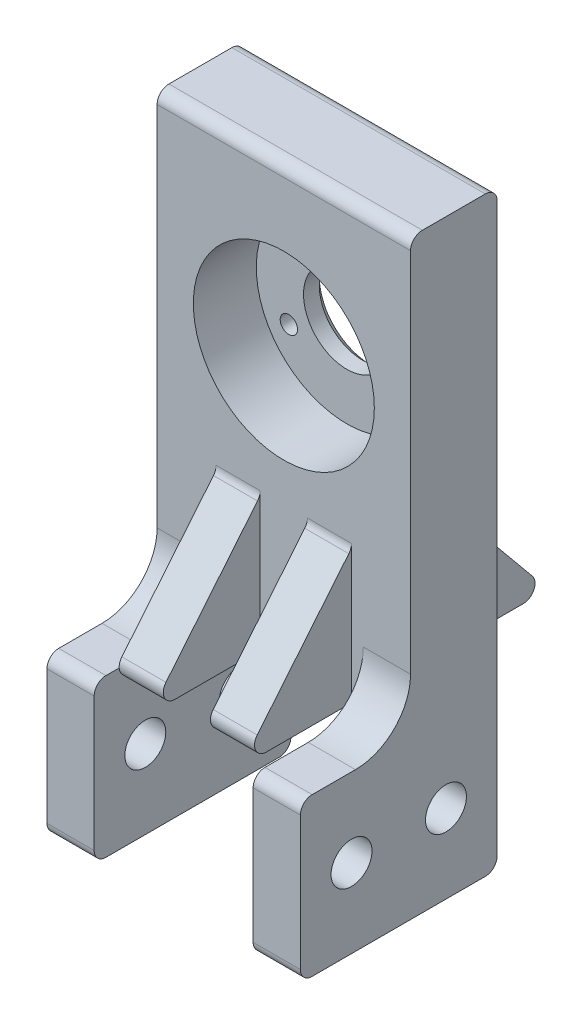
SolidWorks part; units mm, degrees
ref_plane "Front plane" through (0, 0, 0) normal (0, 0, 1) x (1, 0, 0)
ref_plane "Top plane" through (0, 0, 0) normal (0, 1, 0) x (1, 0, 0)
ref_plane "Right plane" through (0, 0, 0) normal (1, 0, 0) x (0, 0, -1)
ref_axis "Axis X" through (0, 0, 0) along (1, 0, 0)
ref_axis "Axis Y" through (0, 0, 0) along (0, 1, 0)
ref_axis "Axis Z" through (0, 0, 0) along (0, 0, 1)
sketch "Sketch1" plane through (0, 0, 0) normal (1, 0, 0) x (0, 0, -1)
  line L1 (5.5, 65.1) -> (-5.5, 65.1)
  line L2 (5.5, 65.1) -> (5.5, 10.1)
  line L3 (5.5, 10.1) -> (-5.5, 10.1)
  line L4 (-5.5, 65.1) -> (-5.5, 10.1)
  line L5 (5.5, 65.1) -> (-5.5, 10.1) construction
  line L6 (5.5, 10.1) -> (-5.5, 65.1) construction
  point P0 (0, 37.6)
  dimension "D1" = 10.1
  dimension "D2" = 11
  dimension "D3" = 55
extrude "Extrude1" add sketch "Sketch1" along normal blind 10.1 and the other way blind 10.1
sketch "Sketch2" plane through (10.1, 0, 0) normal (1, 0, 0) x (0, 0, -1)
  line L0 (5.5, 10.1) -> (5.5, 65.1) construction
  line L1 (19.5, 10) -> (12.5, 10) construction
  line L2 (19.5, 10) -> (19.5, -10) construction
  line L3 (19.5, -10) -> (-19.5, -10) construction
  line L4 (-19.5, 10) -> (-19.5, -10)
  line L5 (19.5, 10) -> (-19.5, -10) construction
  line L6 (19.5, -10) -> (-19.5, 10) construction
  line L7 (-5.5, 65.1) -> (5.5, 65.1)
  line L8 (-5.5, 65.1) -> (-5.5, 17)
  line L9 (-5.5, 10) -> (5.5, 10) construction
  line L10 (5.5, 65.1) -> (5.5, 17)
  line L11 (-12.5, 10) -> (-19.5, 10)
  line L12 (5.5, 10) -> (-5.5, 10) construction
  line L13 (5.5, 17) -> (5.5, -10)
  line L14 (-19.5, -10) -> (5.5, -10)
  arc A0 (12.5, 10) -> (5.5, 17) centre (12.5, 17) cw construction
  arc A1 (-12.5, 10) -> (-5.5, 17) centre (-12.5, 17) ccw
  point P0 (0, 0)
  dimension "D3" = 7
  dimension "D1" = 20
  dimension "D2" = 25
extrude "Extrude2" add sketch "Sketch2" along normal blind 6
mirror "Mirror2" about plane through (0, 0, 0) normal (1, 0, 0) of "Extrude2"
sketch "Sketch5" plane through (0, 0, 5.5) normal (0, 0, 1) x (1, 0, 0)
  line L0 (-16.1, 19.5) -> (16.1, 19.5) construction
  line L1 (-16.1, 65.1) -> (-16.1, 17) construction
  line L2 (16.1, 65.1) -> (16.1, 17) construction
  line L3 (-16.1, 22.3) -> (16.1, 22.3) construction
  line L4 (-16.1, 16.7) -> (16.1, 16.7) construction
  line L5 (-16.1, 54.55) -> (16.1, 54.55) construction
  line L6 (-16.1, 51.75) -> (16.1, 51.75) construction
  line L7 (-16.1, 48.95) -> (16.1, 48.95) construction
  line L8 (-5.5, 44) -> (5.5, 44) construction
  line L9 (-10.1, 10) -> (10.1, 10) construction
  line L10 (-10.1, 10) -> (-10.1, -10) construction
  line L11 (10.1, 10) -> (10.1, -10) construction
  circle A0 centre (0, 44) radius 5.5
  dimension "D5" = 11
  dimension "D1" = 5.6
  dimension "D2" = 5.6
  dimension "D3" = 19.5
  dimension "D4" = 32.25
  dimension "D7" = 10
  dimension "D8" = 34
extrude "Extrude4" cut sketch "Sketch5" against normal through all
sketch "Эскиз1" plane through (16.1, 0, 0) normal (1, 0, 0) x (0, 0, -1)
  line L0 (-19.5, 0) -> (5.5, 0) construction
  line L1 (-19.5, 10) -> (-19.5, -10) construction
  line L2 (5.5, -10) -> (5.5, 65.1) construction
  line L3 (-7, 0) -> (-7, 8.1058) construction
  circle A0 centre (-13, 0) radius 2.6
  circle A2 centre (-1, 0) radius 2.6
  dimension "D1" = 5.2
  dimension "D2" = 12
extrude "Вырез-Вытянуть1" cut sketch "Эскиз1" against normal through all
fillet "Fillet2" radius 1.5 8 edges at (13.1, 10, 19.5) (-13.1, 10, 19.5) (0, 65.1, 5.5) (0, 65.1, -5.5) (13.1, -10, -5.5) (-13.1, -10, -5.5) (-13.1, -10, 19.5) (13.1, -10, 19.5)
sketch "Эскиз3" plane through (0, 0, 5.5) normal (0, 0, 1) x (1, 0, 0)
  circle A0 centre (0, 44) radius 11.5
  dimension "D1" = 23
extrude "Вырез-Вытянуть2" cut sketch "Эскиз3" against normal offset from surface (8 mm away) 3 up to face at (5.5, 44, -5.5)
sketch "Эскиз4" plane through (0, 0, -2.5) normal (0, 0, 1) x (1, 0, 0)
  circle A0 centre (0, 44) radius 8.5 construction
  circle A1 centre (0, 52.5) radius 1.1
  circle A2 centre (7.3612, 39.75) radius 1.1
  circle A3 centre (-7.3612, 39.75) radius 1.1
  dimension "D1" = 17
  dimension "D2" = 2.2
  dimension "D3" = 3
extrude "Вырез-Вытянуть3" cut sketch "Эскиз4" against normal through all
chamfer "Фаска1" distance 1 angle 45 4 edges at (5.5, 44, -5.5) (1.1, 52.5, -5.5) (-6.2612, 39.75, -5.5) (8.4612, 39.75, -5.5)
sketch "Эскиз5" plane through (0, 0, 0) normal (1, 0, 0) x (0, 0, -1)
  line L0 (5.5, 10.1) -> (19.5, 10.1)
  line L1 (-5.5, 10.1) -> (5.5, 10.1) construction
  line L3 (0, 65.1) -> (0, -10) construction
  line L4 (4, 65.1) -> (-4, 65.1) construction
  line L5 (-18, -10) -> (4, -10) construction
  line L6 (-5.5, 10.1) -> (-19.5, 10.1)
  line L7 (-19.5, 8.5) -> (-19.5, -8.5) construction
  line L8 (-5.5, 63.6) -> (-5.5, 17) construction
  line L9 (-19.5, 10.1) -> (-5.5, 27.1)
  line L10 (-5.5, 27.1) -> (-5.5, 10.1)
  line L11 (5.5, 27.1) -> (5.5, 10.1)
  line L12 (19.5, 10.1) -> (5.5, 27.1)
  dimension "D1" = 17
extrude "Бобышка-Вытянуть1" add sketch "Эскиз5" along normal offset from surface 1.5 and the other way offset from surface 1.5 up to face at (10.1, 0, 10.4) other way up to face at (-10.1, 0, 15.6)
fillet "Скругление1" radius 1.5 4 edges at (0, 27.1, 5.5) (0, 27.1, -5.5) (0, 10.1, -19.5) (0, 10.1, 19.5)
sketch "Эскиз6" plane through (0, 0, 0) normal (1, 0, 0) x (0, 0, -1)
  line L0 (-5.5, 63.6) -> (-5.5, 17) construction
  line L1 (-17.8215, 10.1) -> (-5.5, 10.1)
  line L2 (-17.8215, 10.1) -> (-17.8215, 27.6381)
  line L3 (-17.8215, 27.6381) -> (-5.5, 27.6381)
  line L4 (-5.5, 10.1) -> (-5.5, 27.6381)
  line L5 (5.5, 10.1) -> (16.3215, 10.1) construction
  line L6 (0, 65.1) -> (0, -10) construction
  line L7 (4, 65.1) -> (-4, 65.1) construction
  line L8 (-18, -10) -> (4, -10) construction
  line L9 (17.8215, 27.6381) -> (5.5, 27.6381)
  line L10 (5.5, 10.1) -> (5.5, 27.6381)
  line L11 (17.8215, 10.1) -> (5.5, 10.1)
  line L12 (17.8215, 10.1) -> (17.8215, 27.6381)
  arc A0 (-17.4794, 12.5536) -> (-16.3215, 10.1) centre (-16.3215, 11.6) ccw construction
extrude "Вырез-Вытянуть4" cut sketch "Эскиз6" against normal mid plane 6
equation "\"bearing_d1\"= 5"
equation "\"bearing_d2\"= 10"
equation "\"print_offset\"= 0.2"
equation "\"bearing_h\"=15"
equation "\"prof_width\"= 20'Aluminium profile parameters"
equation "\"prof_groove\"= 6"
equation "\"prof_length\"= 410"
equation "\"prof_screw_diameter\"= 4"
equation "\"screw2_diameter\"= 2"
equation "\"screw2_diameter_ext\"= 4"
equation "\"screw2_heigh_head\"= 2"
equation "\"nut2_diameter\"= 4"
equation "\"nut2_heigh\"= 2"
equation "\"screw_offset_ext\"= 2"
equation "\"angle_heigh\"= 50'Angle mount parameters"
equation "\"angle_thikness\"= 3"
equation "\"angle_width\"= 30"
equation "\"mount_thikness\"= 15'Other mounts parameters"
equation "\"mount_screw\"= 4"
equation "\"mount_screw_distance\"= 40"
equation "\"bearings_distance\"= 22"
equation "\"tape_distance\"= 7.35"
equation "\"bearing_grove_d1\"= 4"
equation "\"bearing_grove_d2\"= 13"
equation "\"bearing_grove_h\"= 4"
equation "\"bearing_groove_r\"= 1"
equation "\"D1@Sketch1\"=(\"prof_width\"+\"print_offset\")/2"
equation "\"D1@Extrude1\"=(\"prof_width\"+\"print_offset\")/2"
equation "\"D2@Extrude1\"=(\"prof_width\"+\"print_offset\")/2"
equation "\"D1@Sketch2\"=\"prof_width\""
equation "\"D2@Sketch5\"= \"D1@Sketch5\""
equation "\"D7@Sketch5\"=\"prof_width\"/2"
equation "\"D1@Эскиз1\"=\"print_offset\"+5"
equation "\"D2@Эскиз4\"=\"print_offset\"+2"
equation "\"radial_bearing_d1\"= 6"
equation "\"radial_bearing_d2\"= 13"
equation "\"radial_bearing_h\"= 5"
equation "\"shaft_d\"= 6"
equation "\"shaft_h\"= 50"
equation "\"central_hole_d\"= 20"
equation "\"sitting_screws_d\"= 30"
equation "\"screw_d\"= 2"
equation "\"screw_hh_d\"= 3.4"
equation "\"screw_h\"= 8"
equation "\"screw_hh_h\"= 2"
equation "\"motor_screw_d\"= 4"
equation "\"motor_screw_hh_d\"= 7.4"
equation "\"motor_screw_h\"= 20"
equation "\"motor_screw_hh_h\"= 2.5"
equation "\"motor_nut_d\"= 6.8"
equation "\"motor_nut_h\"= 2.8"
equation "\"nut_d\"= 3.9"
equation "\"nut_h\"= 2"
equation "\"washer_d1\"= 20.3"
equation "\"washer_d2\"= 44"
equation "\"washer_h\"= 4.45"
